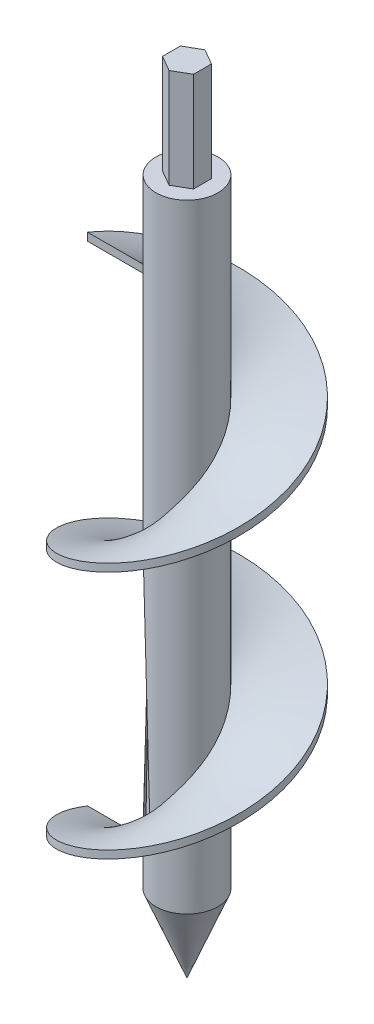
SolidWorks part; units mm, degrees
ref_plane "Front Plane" through (0, 0, 0) normal (0, 0, 1) x (1, 0, 0)
ref_plane "Top Plane" through (0, 0, 0) normal (0, 1, 0) x (1, 0, 0)
ref_plane "Right Plane" through (0, 0, 0) normal (1, 0, 0) x (0, 0, -1)
sketch "Sketch1" plane through (0, 0, 0) normal (0, 0, 1) x (1, 0, 0)
  line L0 (0, 0) -> (7.9375, 0)
  line L1 (7.9375, 0) -> (7.9375, -158.0444)
  line L2 (7.9375, -158.0444) -> (0, -177.8)
  line L4 (0, -177.8) -> (0, 0)
  dimension "D1" = 7.9375
  dimension "D2" = 177.8
  dimension "D3" = 19.7556
revolve "Revolve1" add sketch "Sketch1" angle 360 about L4
sketch "Sketch2" plane through (0, 0, 0) normal (0, 1, 0) x (1, 0, 0)
  line L1 (0, -4.5827) -> (3.9688, -2.2914)
  line L2 (3.9688, -2.2914) -> (3.9687, 2.2914)
  line L3 (3.9687, 2.2914) -> (0, 4.5827)
  line L4 (0, 4.5827) -> (-3.9688, 2.2914)
  line L5 (-3.9688, 2.2914) -> (-3.9688, -2.2914)
  line L6 (-3.9688, -2.2914) -> (0, -4.5827)
  circle A0 centre (0, 0) radius 3.9688 construction
  dimension "D1" = 7.9375
extrude "Boss-Extrude1" add sketch "Sketch2" along normal blind 25.4
ref_plane "Plane1" through (0, -25.4, 0) normal (0, 1, 0) x (1, 0, 0)
sketch "Sketch3" plane through (0, -25.4, 0) normal (0, 1, 0) x (1, 0, 0)
  circle A0 centre (0, 0) radius 25.4
  dimension "D1" = 50.8
curve "Helix/Spiral1" pitch 63.5 height 127 radius 25.4 centre (0, -25.4, 0) axis (0, -1, 0) start towards (0, 0, 1)
sketch "Sketch4" plane through (0, 0, 0) normal (0, 0, 1) x (1, 0, 0)
  line L0 (-7.9375, 0) -> (-7.9375, -158.0444) construction
  line L1 (-7.9375, -25.4) -> (-25.4, -25.4)
  line L2 (-7.9375, -25.4) -> (-7.9375, -27.4)
  line L3 (-7.9375, -27.4) -> (-25.4, -27.4)
  line L4 (-25.4, -25.4) -> (-25.4, -27.4)
  line L5 (0, 0) -> (0, -25.4) construction
  line L6 (8.7312, -25.4) -> (-8.7312, -25.4) construction
  spline S0 degree 3 poles (-25.4, -25.4) (-25.4, -26.3178) (-24.7642, -28.162) (-21.9739, -30.9214) (-17.5538, -33.6827) (-11.8319, -36.4435) (-5.2325, -39.2044) (1.7551, -41.9652) (8.6124, -44.7261) (14.831, -47.487) (19.9497, -50.2478) (23.5887, -53.0087) (25.4784, -55.7696) (25.4784, -58.5304) (23.5887, -61.2913) (19.9497, -64.0522) (14.831, -66.813) (8.6124, -69.5739) (1.7551, -72.3348) (-5.2325, -75.0957) (-11.8319, -77.8565) (-17.5538, -80.6174) (-21.9739, -83.3783) (-24.7642, -86.1391) (-25.7179, -88.9) (-24.7642, -91.6609) (-21.9739, -94.4217) (-17.5538, -97.1826) (-11.8319, -99.9435) (-5.2325, -102.7043) (1.7551, -105.4652) (8.6124, -108.2261) (14.831, -110.987) (19.9497, -113.7478) (23.5887, -116.5087) (25.4784, -119.2696) (25.4784, -122.0304) (23.5887, -124.7913) (19.9497, -127.5522) (14.831, -130.313) (8.6124, -133.0739) (1.7551, -135.8348) (-5.2325, -138.5956) (-11.8319, -141.3565) (-17.5538, -144.1173) (-21.9739, -146.8786) (-24.7642, -149.638) (-25.4, -151.4822) (-25.4, -152.4) knots 0 0 0 0 0.021739 0.043478 0.065217 0.086957 0.108696 0.130435 0.152174 0.173913 0.195652 0.217391 0.23913 0.26087 0.282609 0.304348 0.326087 0.347826 0.369565 0.391304 0.413043 0.434783 0.456522 0.478261 0.5 0.521739 0.543478 0.565217 0.586957 0.608696 0.630435 0.652174 0.673913 0.695652 0.717391 0.73913 0.76087 0.782609 0.804348 0.826087 0.847826 0.869565 0.891304 0.913043 0.934783 0.956522 0.978261 1 1 1 1 construction
  dimension "D1" = 2
  dimension "D2" = 25.4
sweep "Sweep1" add profiles "Sketch4" path "Helix/Spiral1"
